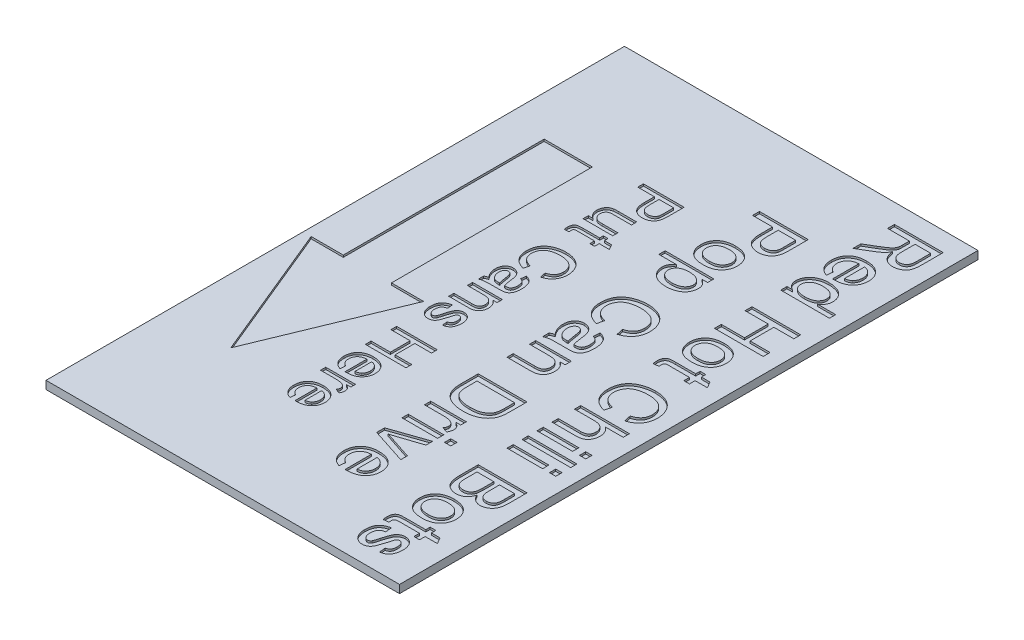
SolidWorks part; units mm, degrees
material "Oak"
ref_plane "Front" through (0, 0, 0) normal (0, 0, 1) x (1, 0, 0)
ref_plane "Top" through (0, 0, 0) normal (0, 1, 0) x (1, 0, 0)
ref_plane "Right" through (0, 0, 0) normal (1, 0, 0) x (0, 0, -1)
sketch "Sketch1" plane through (0, 0, 0) normal (0, 1, 0) x (1, 0, 0)
  line L1 (-279.4, -457.2) -> (279.4, -457.2)
  line L2 (-279.4, -457.2) -> (-279.4, 457.2)
  line L3 (-279.4, 457.2) -> (279.4, 457.2)
  line L4 (279.4, -457.2) -> (279.4, 457.2)
  line L5 (-279.4, -457.2) -> (279.4, 457.2) construction
  line L6 (-279.4, 457.2) -> (279.4, -457.2) construction
  point P0 (0, 0)
  dimension "D1" = 914.4
  dimension "D2" = 558.8
extrude "Boss-Extrude1" add sketch "Sketch1" along normal blind 12.7
sketch "Sketch3" plane through (0, 12.7, 0) normal (0, 1, 0) x (1, 0, 0)
  line L0 (177.8, 457.2) -> (177.8, -457.2) construction
  line L1 (-177.8, 457.2) -> (-177.8, -457.2) construction
  line L7 (-279.4, -457.2) -> (279.4, -457.2) construction
  line L8 (279.4, 457.2) -> (-279.4, 457.2) construction
  line L9 (279.4, -457.2) -> (279.4, 457.2) construction
  line L10 (-76.2, 457.2) -> (-76.2, -457.2) construction
  line L11 (-279.4, 457.2) -> (-279.4, -457.2) construction
  line L12 (-139.7, 266.7) -> (-215.9, 266.7)
  line L13 (-215.9, 266.7) -> (-215.9, -50.8)
  line L14 (-215.9, -50.8) -> (-266.7, -50.8)
  line L15 (-266.7, -50.8) -> (-177.8, -266.7)
  line L16 (-177.8, -266.7) -> (-88.9, -50.8)
  line L17 (-88.9, -50.8) -> (-139.7, -50.8)
  line L18 (-139.7, -50.8) -> (-139.7, 266.7)
  text T0 "Red Hot Chili Bots\r\nPop Can Drive" font "Arial" height in points 300
  text T1 "Put Cans Here" font "Arial" height in points 250
  point P22 (0, 0)
  dimension "D1" = 101.6
  dimension "D2" = 203.2
  dimension "D3" = 76.2
  dimension "D4" = 317.5
  dimension "D5" = 101.6
  dimension "D6" = 190.5
  dimension "D7" = 50.8
  dimension "D8" = 215.9
  dimension "D9" = 38.1
extrude "Cut-Extrude1" cut sketch "Sketch3" against normal blind 3.175
